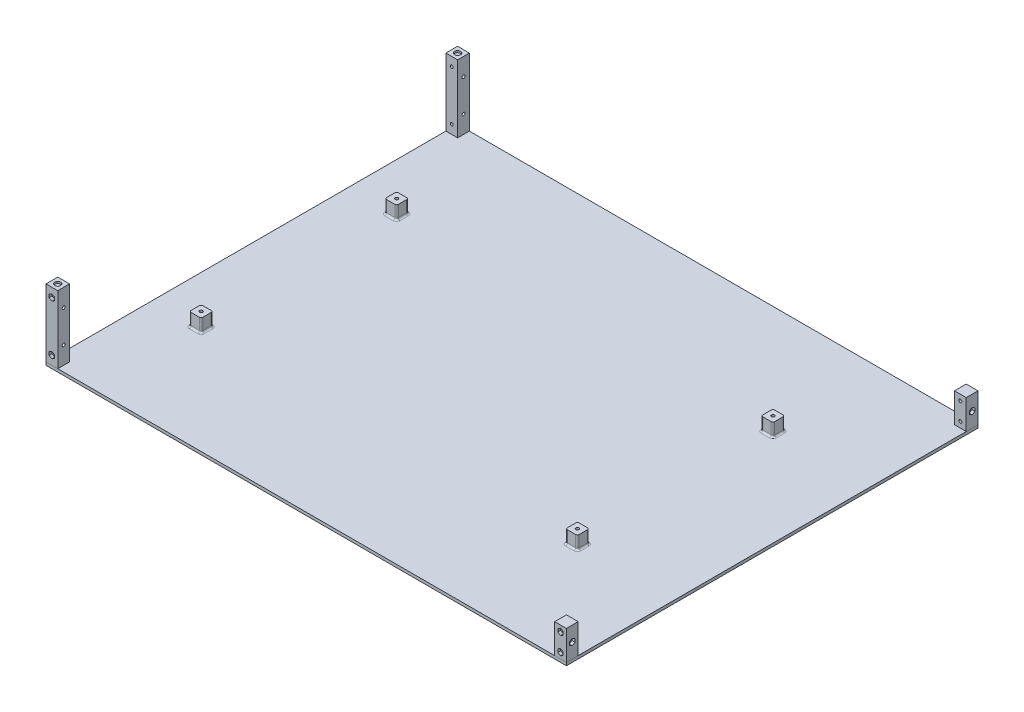
SolidWorks part; units mm, degrees
ref_plane "Front Plane" through (0, 0, 0) normal (0, 0, 1) x (1, 0, 0)
ref_plane "Top Plane" through (0, 0, 0) normal (0, 1, 0) x (1, 0, 0)
ref_plane "Right Plane" through (0, 0, 0) normal (1, 0, 0) x (0, 0, -1)
sketch "Sketch1" plane through (0, 0, 0) normal (0, 1, 0) x (1, 0, 0)
  line L1 (0, 0) -> (885, 0)
  line L2 (0, 0) -> (0, 700)
  line L3 (0, 700) -> (885, 700)
  line L4 (885, 0) -> (885, 700)
  dimension "D1" = 700
  dimension "D2" = 885
extrude "Boss-Extrude1" add sketch "Sketch1" along normal blind 5
sketch "Sketch2" plane through (0, 5, 0) normal (0, 1, 0) x (1, 0, 0)
  line L0 (0, 700) -> (0, 0) construction
  line L1 (720, 516.25) -> (720, 183.75)
  line L2 (885, 700) -> (0, 700) construction
  line L3 (720, 516.25) -> (80, 516.25)
  line L4 (80, 516.25) -> (80, 183.75)
  line L5 (710, 523.25) -> (710, 509.25)
  line L6 (73, 526.25) -> (87, 526.25)
  line L7 (70, 523.25) -> (70, 509.25)
  line L8 (73, 506.25) -> (87, 506.25)
  line L9 (90, 523.25) -> (90, 509.25)
  line L10 (713, 526.25) -> (727, 526.25)
  line L11 (730, 523.25) -> (730, 509.25)
  line L12 (713, 506.25) -> (727, 506.25)
  line L13 (710, 190.75) -> (710, 176.75)
  line L14 (713, 193.75) -> (727, 193.75)
  line L15 (730, 190.75) -> (730, 176.75)
  line L16 (713, 173.75) -> (727, 173.75)
  line L17 (70, 190.75) -> (70, 176.75)
  line L18 (73, 193.75) -> (87, 193.75)
  line L19 (90, 190.75) -> (90, 176.75)
  line L20 (73, 173.75) -> (87, 173.75)
  circle A0 centre (80, 516.25) radius 2.65
  circle A1 centre (720, 516.25) radius 2.65
  circle A2 centre (720, 183.75) radius 2.65
  circle A3 centre (80, 183.75) radius 2.65
  arc A4 (70, 509.25) -> (73, 506.25) centre (73, 509.25) ccw
  arc A5 (87, 506.25) -> (90, 509.25) centre (87, 509.25) ccw
  arc A6 (87, 526.25) -> (90, 523.25) centre (87, 523.25) cw
  arc A7 (73, 526.25) -> (70, 523.25) centre (73, 523.25) ccw
  arc A8 (713, 526.25) -> (710, 523.25) centre (713, 523.25) ccw
  arc A9 (710, 509.25) -> (713, 506.25) centre (713, 509.25) ccw
  arc A10 (727, 526.25) -> (730, 523.25) centre (727, 523.25) cw
  arc A11 (727, 506.25) -> (730, 509.25) centre (727, 509.25) ccw
  arc A12 (713, 193.75) -> (710, 190.75) centre (713, 190.75) ccw
  arc A13 (710, 176.75) -> (713, 173.75) centre (713, 176.75) ccw
  arc A14 (727, 193.75) -> (730, 190.75) centre (727, 190.75) cw
  arc A15 (727, 173.75) -> (730, 176.75) centre (727, 176.75) ccw
  arc A16 (73, 193.75) -> (70, 190.75) centre (73, 190.75) ccw
  arc A17 (70, 176.75) -> (73, 173.75) centre (73, 176.75) ccw
  arc A18 (87, 193.75) -> (90, 190.75) centre (87, 190.75) cw
  arc A19 (87, 173.75) -> (90, 176.75) centre (87, 176.75) ccw
  point P10 (720, 350)
  point P20 (70, 506.25)
  point P23 (90, 506.25)
  point P28 (70, 526.25)
  dimension "D1" = 5.3
  dimension "D11" = 3
  dimension "D2" = 332.5
  dimension "D3" = 332.5
  dimension "D4" = 640
  dimension "D5" = 80
  dimension "D6" = 350
  dimension "D7" = 20
  dimension "D8" = 20
  dimension "D9" = 10
  dimension "D10" = 10
  dimension "D12" = 2
  dimension "D13" = 2
extrude "Boss-Extrude2" add sketch "Sketch2" along normal blind 22.5 contours L20 A19 L19 A18 L18 A3 A16 L17 A17 | L16 A15 L15 A14 L14 A2 A12 L13 A13 | L12 A11 L11 A10 L10 A8 L5 L3 A1 L1 | L5 A9 L12 L1 A1 L3 | L8 A5 L9 L3 A0 L4 | L6 A7 L7 A4 L8 L4 A0 L3 L9 A6 region at (722.0738, 5, -514.1762) region at (714.8594, 5, -511.1094) region at (723.5, 5, -193.4672) region at (83.5, 5, -193.4672) region at (85.1406, 5, -511.1094) region at (86.325, 5, -516.5328)
sketch "Sketch4" plane through (0, 5, 0) normal (0, 1, 0) x (1, 0, 0)
  circle A0 centre (80, 516.25) radius 5
  circle A1 centre (720, 516.25) radius 5
  circle A2 centre (720, 183.75) radius 5
  circle A3 centre (80, 183.75) radius 5
  dimension "D1" = 10
extrude "Cut-Extrude1" cut sketch "Sketch4" against normal blind 30
fillet "Fillet1" radius 3 32 edges at (710.8787, 5, -192.8713) (720, 5, -193.75) (729.1213, 5, -192.8713) (730, 5, -183.75) (729.1213, 5, -174.6287) (720, 5, -173.75) (710.8787, 5, -174.6287) (710.8787, 5, -525.3713) (720, 5, -526.25) (729.1213, 5, -525.3713) (730, 5, -516.25) (729.1213, 5, -507.1287) (720, 5, -506.25) (710.8787, 5, -507.1287) (70.8787, 5, -525.3713) (80, 5, -526.25) (89.1213, 5, -525.3713) (90, 5, -516.25) (89.1213, 5, -507.1287) (80, 5, -506.25) (70.8787, 5, -507.1287) (70.8787, 5, -192.8713) (80, 5, -193.75) (89.1213, 5, -192.8713) (90, 5, -183.75) (89.1213, 5, -174.6287) (80, 5, -173.75) (70.8787, 5, -174.6287) (710, 5, -183.75) (710, 5, -516.25) (70, 5, -516.25) (70, 5, -183.75)
sketch "Sketch5" plane through (0, 5, 0) normal (0, 1, 0) x (1, 0, 0)
  line L1 (0, 0) -> (20, 0)
  line L2 (0, 0) -> (0, 20)
  line L3 (0, 20) -> (20, 20)
  line L4 (20, 0) -> (20, 20)
  line L5 (0, 700) -> (20, 700)
  line L6 (0, 700) -> (0, 680)
  line L7 (0, 680) -> (20, 680)
  line L8 (20, 700) -> (20, 680)
  dimension "D1" = 20
  dimension "D2" = 20
  dimension "D3" = 20
  dimension "D4" = 20
extrude "Boss-Extrude3" add sketch "Sketch5" along normal blind 115
sketch "Sketch6" plane through (0, 5, 0) normal (0, 1, 0) x (1, 0, 0)
  line L1 (885, 0) -> (865, 0)
  line L2 (885, 0) -> (885, 20)
  line L3 (885, 20) -> (865, 20)
  line L4 (865, 0) -> (865, 20)
  line L5 (885, 700) -> (865, 700)
  line L6 (885, 700) -> (885, 680)
  line L7 (885, 680) -> (865, 680)
  line L8 (865, 700) -> (865, 680)
  dimension "D1" = 20
  dimension "D2" = 20
  dimension "D3" = 20
  dimension "D4" = 20
extrude "Boss-Extrude4" add sketch "Sketch6" along normal blind 50
sketch "Sketch7" plane through (20, 0, 0) normal (1, 0, 0) x (0, 0, -1)
  line L0 (0, 120) -> (20, 120) construction
  line L2 (0, 5) -> (20, 5) construction
  line L3 (20, 120) -> (20, 5) construction
  circle A0 centre (10, 90) radius 2.5
  circle A1 centre (10, 35) radius 2.5
  dimension "D3" = 5
  dimension "D4" = 5
  dimension "D1" = 30
  dimension "D2" = 30
  dimension "D5" = 10
  dimension "D6" = 10
extrude "Cut-Extrude2" cut sketch "Sketch7" against normal blind 50
sketch "Sketch8" plane through (0, 0, 0) normal (-1, 0, 0) x (0, 0, 1)
  line L6 (-10, 84.6306) -> (-5.35, 87.3153)
  line L7 (-5.35, 87.3153) -> (-5.35, 92.6847)
  line L8 (-10, 84.6306) -> (-14.65, 87.3153)
  line L9 (-14.65, 87.3153) -> (-14.65, 92.6847)
  line L10 (-14.65, 92.6847) -> (-10, 95.3694)
  line L11 (-10, 95.3694) -> (-5.35, 92.6847)
  circle A0 centre (-10, 90) radius 4.65
  circle M14 centre (-10, 90) radius 2.5
  dimension "D1" = 9.3
extrude "Cut-Extrude3" cut sketch "Sketch8" against normal blind 5 contours A0 M14 | A0 L8 L6 | A0 L6 L7 | A0 L7 L11 | A0 L11 L10 | A0 L10 L9 | A0 L9 L8 region at (0, 85.1939, -10) region at (0, 87.597, -5.8378) region at (0, 85.4815, -10) region at (0, 87.597, -14.1622) region at (0, 92.403, -5.8378) region at (0, 92.403, -14.1622) region at (0, 94.8061, -10)
pattern_linear "LPattern1" count 2 spacing 55 along (0, -1, 0) of "Cut-Extrude3"
pattern_linear "LPattern2" count 2 spacing 680 along (0, 0, -1) count 2 spacing 55 along (0, -1, 0) of "Cut-Extrude3", "Cut-Extrude2"
sketch "Sketch9" plane through (0, 0, 0) normal (0, 0, 1) x (1, 0, 0)
  line L0 (0, 120) -> (20, 120) construction
  line L1 (0, 0) -> (885, 0) construction
  line L2 (0, 120) -> (0, 0) construction
  circle A0 centre (10, 105) radius 2.5
  circle A1 centre (10, 20) radius 2.5
  dimension "D1" = 5
  dimension "D2" = 5
  dimension "D3" = 15
  dimension "D4" = 20
  dimension "D5" = 10
  dimension "D6" = 10
extrude "Cut-Extrude4" cut sketch "Sketch9" against normal up to next
sketch "Sketch10" plane through (0, 0, 0) normal (0, 0, 1) x (1, 0, 0)
  line L0 (10, 99.6306) -> (14.65, 102.3153)
  line L1 (14.65, 102.3153) -> (14.65, 107.6847)
  line L2 (10, 99.6306) -> (5.35, 102.3153)
  line L3 (5.35, 102.3153) -> (5.35, 107.6847)
  line L4 (5.35, 107.6847) -> (10, 110.3694)
  line L5 (10, 110.3694) -> (14.65, 107.6847)
  line L6 (10, 14.6306) -> (14.65, 17.3153)
  line L7 (14.65, 17.3153) -> (14.65, 22.6847)
  line L8 (10, 14.6306) -> (5.35, 17.3153)
  line L9 (5.35, 17.3153) -> (5.35, 22.6847)
  line L10 (5.35, 22.6847) -> (10, 25.3694)
  line L11 (10, 25.3694) -> (14.65, 22.6847)
  circle A0 centre (10, 105) radius 4.65
  circle A1 centre (10, 105) radius 2.5 construction
  circle A2 centre (10, 20) radius 4.65
  circle A3 centre (10, 20) radius 2.5 construction
  circle M9 centre (10, 105) radius 2.5
  circle M10 centre (10, 20) radius 2.5
  dimension "D1" = 0
  dimension "D2" = 9.3
  dimension "D3" = 9.3
  dimension "D4" = 0
extrude "Cut-Extrude5" cut sketch "Sketch10" against normal blind 5 contours A0 M9 | A0 L0 L1 | A0 L1 L5 | A0 L5 L4 | A0 L4 L3 | A0 L3 L2 | A0 L2 L0 | A2 L6 L7 | A2 M10 | A2 L7 L11 | A2 L11 L10 | A2 L10 L9 | A2 L9 L8 | A2 L8 L6 | A0 region at (10, 100.1939, 0) region at (14.1622, 102.597, 0) region at (10, 100.4815, 0) region at (5.8378, 102.597, 0) region at (14.1622, 107.403, 0) region at (5.8378, 107.403, 0) region at (10, 109.8061, 0) region at (10, 15.1939, 0) region at (14.1622, 17.597, 0) region at (10, 15.4815, 0) region at (5.8378, 17.597, 0) region at (14.1622, 22.403, 0) region at (5.8378, 22.403, 0) region at (10, 24.8061, 0)
ref_plane "Plane1" through (0, 0, -350) normal (0, 0, -1) x (-1, 0, 0)
mirror "Mirror1" about plane through (0, 0, -350) normal (0, 0, -1) of "Cut-Extrude5", "Cut-Extrude4"
sketch "Sketch11" plane through (0, 0, -20) normal (0, 0, -1) x (-1, 0, 0)
  line L0 (-865, 55) -> (-865, 5) construction
  line L1 (-885, 5) -> (-865, 5) construction
  line L2 (-885, 55) -> (-865, 55) construction
  circle A0 centre (-875, 45) radius 2.65
  circle A1 centre (-875, 15) radius 2.65
  dimension "D1" = 5.3
  dimension "D2" = 5.3
  dimension "D3" = 10
  dimension "D4" = 10
  dimension "D5" = 10
  dimension "D6" = 10
extrude "Cut-Extrude6" cut sketch "Sketch11" against normal blind 20
sketch "Sketch12" plane through (865, 0, 0) normal (-1, 0, 0) x (0, 0, 1)
  line L1 (-20, 55) -> (0, 55) construction
  line L2 (0, 55) -> (0, 5) construction
  circle A1 centre (-10, 30) radius 2.65
  dimension "D3" = 5.3
  dimension "D1" = 25
  dimension "D2" = 10
extrude "Cut-Extrude7" cut sketch "Sketch12" against normal blind 20
sketch "Sketch13" plane through (0, 0, 0) normal (0, 0, 1) x (1, 0, 0)
  line L0 (875, 39.6306) -> (879.65, 42.3153)
  line L1 (879.65, 42.3153) -> (879.65, 47.6847)
  line L2 (875, 39.6306) -> (870.35, 42.3153)
  line L3 (870.35, 42.3153) -> (870.35, 47.6847)
  line L4 (870.35, 47.6847) -> (875, 50.3694)
  line L5 (875, 50.3694) -> (879.65, 47.6847)
  line L6 (875, 9.6306) -> (879.65, 12.3153)
  line L7 (879.65, 12.3153) -> (879.65, 17.6847)
  line L8 (875, 9.6306) -> (870.35, 12.3153)
  line L9 (870.35, 12.3153) -> (870.35, 17.6847)
  line L10 (870.35, 17.6847) -> (875, 20.3694)
  line L11 (875, 20.3694) -> (879.65, 17.6847)
  circle A0 centre (875, 45) radius 4.65
  circle A2 centre (875, 15) radius 4.65
  dimension "D2" = 9.3
  dimension "D3" = 9.3
extrude "Cut-Extrude8" cut sketch "Sketch13" against normal blind 5 contours L7 L11 L10 L9 L8 L6 | L0 L1 L5 L4 L3 L2
sketch "Sketch14" plane through (885, 0, 0) normal (1, 0, 0) x (0, 0, -1)
  line L0 (10, 24.6306) -> (14.65, 27.3153)
  line L1 (14.65, 27.3153) -> (14.65, 32.6847)
  line L2 (10, 24.6306) -> (5.35, 27.3153)
  line L3 (5.35, 27.3153) -> (5.35, 32.6847)
  line L4 (5.35, 32.6847) -> (10, 35.3694)
  line L5 (10, 35.3694) -> (14.65, 32.6847)
  circle A0 centre (10, 30) radius 4.65
  dimension "D2" = 9.3
extrude "Cut-Extrude9" cut sketch "Sketch14" against normal blind 5 contours L5 L1 L0 L2 L3 L4
mirror "Mirror2" about plane through (0, 0, -350) normal (0, 0, -1) of "Cut-Extrude9", "Cut-Extrude8", "Cut-Extrude7", "Cut-Extrude6"
sketch "Sketch15" plane through (0, 120, 0) normal (0, 1, 0) x (1, 0, 0)
  line L0 (20, 20) -> (0, 20) construction
  line L1 (0, 20) -> (0, 0) construction
  circle A0 centre (10, 10) radius 5.1
  dimension "D1" = 10.2
  dimension "D2" = 10
  dimension "D3" = 10
extrude "Cut-Extrude10" cut sketch "Sketch15" against normal blind 3.2
ref_plane "Plane2" through (0, 0, -350) normal (0, 0, 1) x (1, 0, 0)
mirror "Mirror3" about plane through (0, 0, -350) normal (0, 0, 1) of "Cut-Extrude10"
split "Split1" bodies to split 119 resulting bodies 120 121 122 123 124 125 126 127 128 split by face at (720, 5, -183.75)
